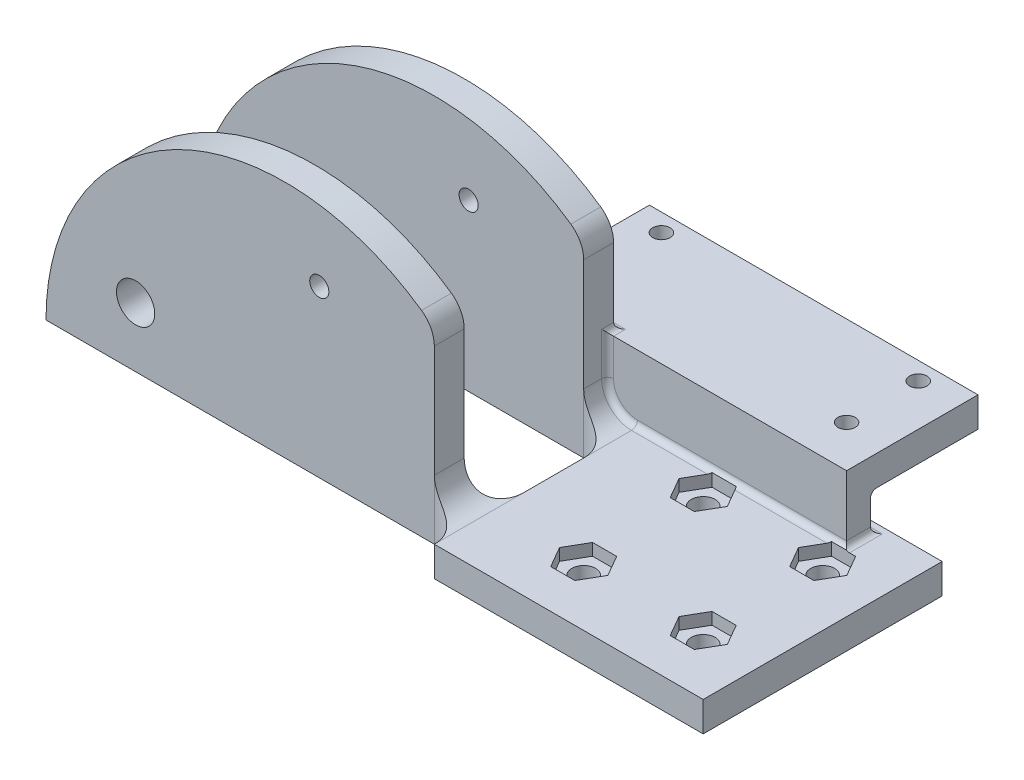
SolidWorks part; units mm, degrees
material "ABS"
ref_plane "Front Plane" through (0, 0, 0) normal (0, 0, 1) x (1, 0, 0)
ref_plane "Top Plane" through (0, 0, 0) normal (0, 1, 0) x (1, 0, 0)
ref_plane "Right Plane" through (0, 0, 0) normal (1, 0, 0) x (0, 0, -1)
sketch "SHAFT LOCATIONS" plane through (0, 0, 0) normal (0, 0, 1) x (1, 0, 0)
  line L0 (-80, 10) -> (-49.2561, 27.75) construction
  line L1 (-49.2561, 27.75) -> (-17.8635, 36.1616) construction
  line L2 (36.4641, 0) -> (-36.4641, 0) construction
  circle A0 centre (-80, 10) radius 3.2
  circle A1 centre (-49.2561, 27.75) radius 1.6
  circle A2 centre (-17.8635, 36.1616) radius 1.6
  dimension "D1" = 6.4
  dimension "D4" = 3.2
  dimension "D5" = 3.2
  dimension "D2" = 80
  dimension "D3" = 10
  dimension "D6" = 35.5
  dimension "D7" = 32.5
  dimension "D8" = 30
  dimension "D9" = 15
ref_plane "LEFT LEG Wall" through (0, 0, 10) normal (0, 0, 1) x (1, 0, 0)
sketch "Sketch1" plane through (0, 0, 0) normal (0, 1, 0) x (1, 0, 0)
  line L1 (-25, 20) -> (20, 20)
  line L2 (-25, 20) -> (-25, -20)
  line L3 (-25, -20) -> (20, -20)
  line L4 (20, 20) -> (20, -20)
  dimension "D1" = 40
  dimension "D2" = 20
  dimension "D3" = 20
  dimension "D4" = 45
extrude "Connection_Base" add sketch "Sketch1" along normal blind 5
sketch "Sketch9" plane through (0, 0, 10) normal (0, 0, 1) x (1, 0, 0)
  line L0 (-25, 0) -> (20, 0) construction
  line L7 (-30, 5) -> (-30, 31.225)
  line L11 (0, 0) -> (-95, 0)
  line L12 (0, 0) -> (0, 5)
  line L13 (-95, 0) -> (-95, 13.3733) construction
  line L18 (0, 5) -> (-30, 5)
  line L20 (-25, 5) -> (-25, 0) construction
  circle A3 centre (-80, 10) radius 3.2 construction
  circle A6 centre (-80, 10) radius 3.2
  circle A7 centre (-49.2561, 27.75) radius 1.6 construction
  circle A8 centre (-49.2561, 27.75) radius 1.6
  arc A12 (-95, 0) -> (-30, 31.225) centre (-55, 0) cw
  point P19 (-54.9111, 2.5)
  point P28 (-38.4151, 28.2356)
  point P32 (-49.2561, 11.4719)
  dimension "D4" = 95
  dimension "D1" = 5
  dimension "D3" = 40
  dimension "D2" = 5
extrude "LEFT_LEG" add sketch "Sketch9" along normal blind 5
fillet "Hub_Fillet" radius 5 2 edges at (-30, 31.225, 12.5) (-30, 5, 12.5)
fillet "Side Fillet" radius 5 2 edges at (-25, 2.5, 10) (-25, 2.5, 15)
mirror "Mirror1" about plane through (0, 0, 0) normal (0, 0, 1) of "Side Fillet", "LEFT_LEG", "Hub_Fillet"
sketch "Sketch2" plane through (0, 5, 0) normal (0, 1, 0) x (1, 0, 0)
  circle A0 centre (-10, 10) radius 2
  dimension "D1" = 4
  dimension "D2" = 10
  dimension "D3" = 10
extrude "Base_Conn_Hole" cut sketch "Sketch2" against normal through all
sketch "Sketch3" plane through (0, 5, 0) normal (0, 1, 0) x (1, 0, 0)
  line L0 (20, 20) -> (-25, 20) construction
  line L1 (-7.9793, 6.5) -> (-5.9585, 10)
  line L2 (-5.9585, 10) -> (-7.9793, 13.5)
  line L3 (-7.9793, 13.5) -> (-12.0207, 13.5)
  line L4 (-12.0207, 13.5) -> (-14.0415, 10)
  line L5 (-14.0415, 10) -> (-12.0207, 6.5)
  line L6 (-12.0207, 6.5) -> (-7.9793, 6.5)
  circle A0 centre (-10, 10) radius 3.5 construction
  dimension "D1" = 7
extrude "Base_Conn_Nut" cut sketch "Sketch3" against normal blind 2
pattern_linear "Base_Holes_Pattern" count 2 spacing 20 along (0, 0, 1) count 2 spacing 20 along (1, 0, 0) of "Base_Conn_Hole", "Base_Conn_Nut"
sketch "Sketch4" plane through (0, 5, 0) normal (0, 1, 0) x (1, 0, 0)
  line L0 (20, -20) -> (20, 20) construction
  line L1 (10, 14) -> (-45, 14)
  line L2 (10, 14) -> (10, 18)
  line L3 (10, 18) -> (-45, 18)
  line L4 (-45, 14) -> (-45, 18)
  line L6 (20, 20) -> (-25, 20) construction
  dimension "D1" = 10
  dimension "D2" = 4
  dimension "D3" = 55
  dimension "D4" = 2
extrude "Motor_Step" add sketch "Sketch4" along normal blind 6.16
sketch "Sketch5" plane through (0, 11.16, 0) normal (0, 1, 0) x (1, 0, 0)
  line L6 (10, 14) -> (-45, 14)
  line L7 (10, 14) -> (10, 36)
  line L8 (10, 36) -> (-45, 36)
  line L9 (-45, 14) -> (-45, 36)
  line L10 (10, 14) -> (-45, 36) construction
  line L11 (10, 36) -> (-45, 14) construction
  point P5 (-17.5, 25)
  dimension "D1" = 22
  dimension "D2" = 55
extrude "Motor_Shelf" add sketch "Sketch5" along normal blind 5
hole_wizard "Motor_M3.5x0.6 Tapped Hole1" positions "Sketch7" profile "Sketch8" tap size "M3.5x0.6" standard "ANSI Metric" end condition up to next
sketch "Sketch7" plane through (0, 16.16, 0) normal (0, 1, 0) x (1, 0, 0)
  line L1 (10, 36) -> (-45, 36) construction
  line L2 (10, 14) -> (10, 36) construction
  point P0 (3, 21)
  point P2 (3, 33)
  point P4 (-40, 33)
  point P6 (-40, 21)
  dimension "D1" = 12
  dimension "D2" = 43
  dimension "D3" = 7
  dimension "D4" = 3
sketch "Sketch8" plane through (3, 16.16, -21) normal (1, 0, 0) x (0, 0, 1)
  line L0 (0, 0) -> (0, 5)
  line L1 (0, 5) -> (1.45, 5)
  line L2 (1.45, 5) -> (1.45, 0)
  line L5 (1.45, 0) -> (0, 0)
  line L11 (0, -6.35) -> (0, 107.95) construction
  dimension "Thru Tap Drill Dia." = 2.9
  dimension "Thru Tap Drill Depth" = 5
cosmetic thread "Hole Thread1" parameters "D2"=3.5
cosmetic thread "Hole Thread2" parameters "D2"=3.5
cosmetic thread "Hole Thread3" parameters "D2"=3.5
cosmetic thread "Hole Thread4" parameters "D2"=3.5
fillet "Fillet2" radius 1 8 edges at (-27.2614, 5, -15.8167) (-30, 13.08, -14) (-28.5355, 6.4645, -14) (-37.5, 5, -15) (-45, 10.58, -15) (-37.5, 16.16, -15) (-30, 16.16, -14.5) (-7.5, 5, -14)
fillet "Fillet3" radius 1 3 edges at (-25.2089, 5.0044, -18) (10, 5, -15.75) (-7.5, 5, -18)
fillet "Fillet4" radius 1 1 edges at (-17.5, 11.16, -18)
